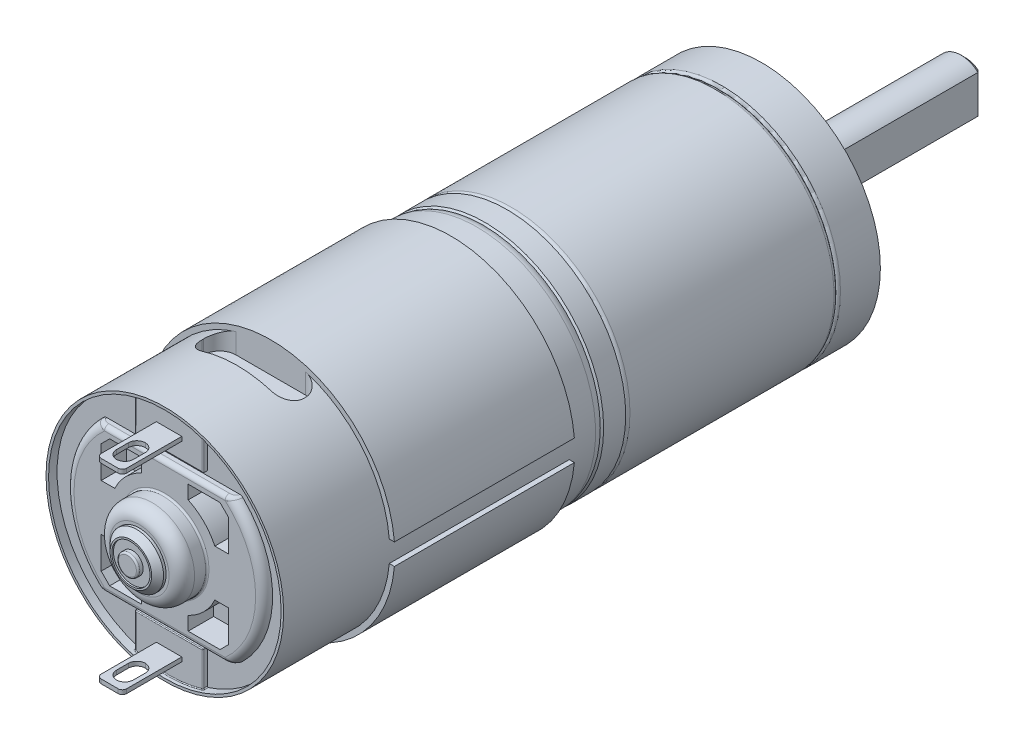
SolidWorks part; units mm, degrees
ref_plane "Front Plane" through (0, 0, 0) normal (0, 0, 1) x (1, 0, 0)
ref_plane "Top Plane" through (0, 0, 0) normal (0, 1, 0) x (1, 0, 0)
ref_plane "Right Plane" through (0, 0, 0) normal (1, 0, 0) x (0, 0, -1)
sketch "Sketch1" plane through (0, 0, 0) normal (0, 0, 1) x (1, 0, 0)
  circle A0 centre (0, 0) radius 14
  dimension "D1" = 28
extrude "Boss-Extrude1" add sketch "Sketch1" along normal blind 5
fillet "Fillet1" radius 0.3 1 edges at (14, 0, 5)
sketch "Sketch2" plane through (0, 0, 5) normal (0, 0, 1) x (1, 0, 0)
  circle A0 centre (0, 0) radius 14
  dimension "D1" = 28
extrude "Boss-Extrude2" add sketch "Sketch2" along normal blind 25
fillet "Fillet2" radius 0.5 2 edges at (14, 0, 30) (14, 0, 5)
sketch "Sketch3" plane through (0, 0, 30) normal (0, 0, 1) x (1, 0, 0)
  circle A0 centre (0, 0) radius 14
extrude "Boss-Extrude3" add sketch "Sketch3" along normal blind 2.8
chamfer "Chamfer1" distance 0.2 angle 45 1 edges at (14, 0, 32.8)
sketch "Sketch4" plane through (0, 0, 32.8) normal (0, 0, 1) x (1, 0, 0)
  circle A0 centre (0, 0) radius 14
extrude "Boss-Extrude4" add sketch "Sketch4" along normal blind 37.5
fillet "Fillet3" radius 1.5 1 edges at (14, 0, 32.8)
sketch "Sketch5" plane through (0, 0, 70.3) normal (0, 0, 1) x (1, 0, 0)
  circle A0 centre (0, 0) radius 13.7
  circle A1 centre (0, 0) radius 14 construction
  dimension "D1" = 0.3
extrude "Cut-Extrude1" cut sketch "Sketch5" against normal blind 1
sketch "Sketch6" plane through (0, 0, 69.3) normal (0, 0, 1) x (1, 0, 0)
  line L0 (0, 8.5) -> (0, -8.5) construction
  line L1 (8.0399, -8.5) -> (-8.0399, -8.5)
  line L2 (8.0399, 8.5) -> (-8.0399, 8.5)
  circle A0 centre (0, 0) radius 11.7
  circle A1 centre (0, 0) radius 13.7 construction
  point P8 (0, 0)
  point P11 (0, -8.5)
  point P14 (0, 8.5)
  dimension "D1" = 2
  dimension "D2" = 17
extrude "Boss-Extrude5" add sketch "Sketch6" along normal blind 1 contours L2 L0 L1 A0 | L0 L2 A0 L1 region at (5.3371, 0, 69.3) region at (-5.3371, 0, 69.3)
fillet "Fillet4" radius 1 2 edges at (-11.7, 0, 70.3) (11.7, 0, 70.3)
fillet "Fillet5" radius 0.5 6 edges at (7.6727, 8.5, 69.9605) (-7.8613, 8.5, 69.7787) (7.8613, -8.5, 69.7787) (-7.6727, -8.5, 69.9605) (0, 8.5, 70.3) (0, -8.5, 70.3)
sketch "Sketch7" plane through (0, 0, 70.3) normal (0, 0, 1) x (1, 0, 0)
  circle A0 centre (0, 0) radius 5
  dimension "D1" = 10
extrude "Boss-Extrude6" add sketch "Sketch7" along normal blind 3
fillet "Fillet6" radius 1.5 1 edges at (5, 0, 73.3)
fillet "Fillet7" radius 0.2 1 edges at (5, 0, 70.3)
sketch "Sketch8" plane through (0, 0, 73.3) normal (0, 0, 1) x (1, 0, 0)
  circle A0 centre (0, 0) radius 2.25
  circle A1 centre (0, 0) radius 3.15
  dimension "D1" = 6.3
  dimension "D2" = 4.5
extrude "Boss-Extrude7" add sketch "Sketch8" along normal blind 1
chamfer "Chamfer2" distance 0.7 angle 45 1 edges at (3.15, 0, 74.3)
sketch "Sketch9" plane through (0, 0, 73.3) normal (0, 0, 1) x (1, 0, 0)
  circle A0 centre (0, 0) radius 2.25
  circle A1 centre (0, 0) radius 1.25
  dimension "D1" = 2.5
extrude "Boss-Extrude8" add sketch "Sketch9" along normal blind 0.8
sketch "Sketch10" plane through (0, 0, 73.3) normal (0, 0, 1) x (1, 0, 0)
  circle A0 centre (0, 0) radius 1.25
extrude "Boss-Extrude10" add sketch "Sketch10" along normal blind 1.4
fillet "Fillet8" radius 0.2 1 edges at (1.25, 0, 74.7)
sketch "Sketch11" plane through (0, 0, 69.3) normal (0, 0, 1) x (1, 0, 0)
  line L0 (0, 9) -> (0, -9)
  line L1 (4, 9) -> (-4, 9)
  line L2 (-4, 9) -> (-4, 13.1031)
  line L3 (4, 9) -> (4, 13.1031)
  line L4 (0, 0) -> (8.5763, 0) construction
  line L5 (4, -9) -> (4, -13.1031)
  line L6 (-4, -9) -> (-4, -13.1031)
  line L7 (4, -9) -> (-4, -9)
  circle A0 centre (0, 0) radius 13.7
  point P7 (0, 0)
  point P14 (0, 9)
  circle M12 centre (0, 0) radius 13.7
  dimension "D3" = 27.4
  dimension "D1" = 18
  dimension "D2" = 8
extrude "Boss-Extrude12" add sketch "Sketch11" along normal blind 0.5 contours L5 L7 L6 M12 | L1 L3 L2 M12 region at (0, 11.2549, 69.3) region at (0, -11.2549, 69.3)
fillet "Fillet9" radius 0.1 12 edges at (-4, 13.1031, 69.55) (4, 13.1031, 69.55) (-4, -13.1031, 69.55) (4, -13.1031, 69.55) (-4, 11.0515, 69.8) (0, 13.7, 69.8) (4, 11.0515, 69.8) (0, 9, 69.8) (0, -13.7, 69.8) (-4, -11.0515, 69.8) (0, -9, 69.8) (4, -11.0515, 69.8)
sketch "Sketch12" plane through (0, 0, 69.8) normal (0, 0, 1) x (1, 0, 0)
  line L0 (0, 0) -> (0, -11.5) construction
  line L1 (-1.5, -11.5) -> (1.5, -11.5)
  line L2 (1.5, -11.5) -> (1.5, -11)
  line L3 (1.5, -11) -> (-1.5, -11)
  line L4 (-1.5, -11) -> (-1.5, -11.5)
  line L5 (0, 0) -> (-7.3114, 0) construction
  line L6 (-1.5, 11) -> (-1.5, 11.5)
  line L7 (1.5, 11) -> (-1.5, 11)
  line L8 (1.5, 11.5) -> (1.5, 11)
  line L9 (-1.5, 11.5) -> (1.5, 11.5)
  point P6 (0, -11.5)
  point P13 (0, 11.5)
  dimension "D1" = 11.5
  dimension "D2" = 3
  dimension "D3" = 0.5
extrude "Boss-Extrude13" add sketch "Sketch12" along normal blind 7
sketch "Sketch13" plane through (0, -11.5, 0) normal (0, -1, 0) x (1, 0, 0)
  line L0 (0, 76.8) -> (0, 70.3) construction
  line L1 (-1.5, 76.8) -> (1.5, 76.8) construction
  line L2 (14, 70.3) -> (-14, 70.3) construction
  line L3 (-1.5, 76.8) -> (-1.5, 69.8) construction
  line L4 (1, 72.6) -> (-1, 72.6)
  line L5 (1, 72.6) -> (1, 76)
  line L6 (1, 76) -> (-1, 76)
  line L7 (-1, 72.6) -> (-1, 76)
  line L8 (1, 72.6) -> (-1, 76) construction
  line L9 (1, 76) -> (-1, 72.6) construction
  point P6 (0, 74.3)
  dimension "D1" = 2.5
  dimension "D2" = 0.8
  dimension "D3" = 0.5
extrude "Cut-Extrude2" cut sketch "Sketch13" against normal blind 1
fillet "Fillet10" radius 0.5 2 edges at (1.5, -11.25, 76.8) (-1.5, -11.25, 76.8)
ref_plane "Plane1" through (0, 0, 0) normal (0, 1, 0) x (1, 0, 0)
mirror "Mirror6" about plane through (0, 0, 0) normal (0, 1, 0) of "Cut-Extrude2"
fillet "Fillet11" radius 0.5 2 edges at (-1.5, 11.25, 76.8) (1.5, 11.25, 76.8)
sketch "Sketch14" plane through (0, 0, 70.3) normal (0, 0, 1) x (1, 0, 0)
  line L1 (7.5, -7.5) -> (-7.5, -7.5)
  line L2 (7.5, -7.5) -> (7.5, 7.5)
  line L3 (7.5, 7.5) -> (-7.5, 7.5)
  line L4 (-7.5, -7.5) -> (-7.5, 7.5)
  line L5 (7.5, -7.5) -> (-7.5, 7.5) construction
  line L6 (7.5, 7.5) -> (-7.5, -7.5) construction
  line L7 (2.75, -19.1882) -> (-2.75, -19.1882)
  line L8 (2.75, -19.1882) -> (2.75, 19.1882)
  line L9 (2.75, 19.1882) -> (-2.75, 19.1882)
  line L10 (-2.75, -19.1882) -> (-2.75, 19.1882)
  line L11 (2.75, -19.1882) -> (-2.75, 19.1882) construction
  line L12 (2.75, 19.1882) -> (-2.75, -19.1882) construction
  line L13 (-15.3123, -2.75) -> (15.3123, -2.75)
  line L14 (-15.3123, -2.75) -> (-15.3123, 2.75)
  line L15 (-15.3123, 2.75) -> (15.3123, 2.75)
  line L16 (15.3123, -2.75) -> (15.3123, 2.75)
  line L17 (-15.3123, -2.75) -> (15.3123, 2.75) construction
  line L18 (-15.3123, 2.75) -> (15.3123, -2.75) construction
  circle A0 centre (0, 0) radius 6.5
  dimension "D1" = 13
  dimension "D2" = 15
  dimension "D3" = 15
  dimension "D4" = 5.5
  dimension "D5" = 5.5
extrude "Cut-Extrude3" cut sketch "Sketch14" against normal blind 3 contours A0 L13 L4 L1 L10 | A0 L10 L3 L4 L15 | A0 L15 L2 L3 L8 | A0 L8 L1 L2 L13 region at (5.5716, -5.5716, 70.3) region at (-5.5716, -5.5716, 70.3) region at (5.5716, 5.5716, 70.3) region at (-5.5716, 5.5716, 70.3)
chamfer "Chamfer3" distance 1 angle 45 4 edges at (-7.5, 7.5, 68.8) (7.5, 7.5, 68.8) (7.5, -7.5, 68.8) (-7.5, -7.5, 68.8)
sketch "Sketch15" plane through (0, 0, 0) normal (0, 0, -1) x (-1, 0, 0)
  circle A0 centre (0, 0) radius 8.5
  circle A1 centre (0, 0) radius 6.5
  dimension "D1" = 17
  dimension "D2" = 13
extrude "Boss-Extrude14" add sketch "Sketch15" along normal blind 1
fillet "Fillet12" radius 0.1 2 edges at (-8.5, 0, -1) (-6.5, 0, -1)
sketch "Sketch16" plane through (0, 0, 0) normal (0, 0, -1) x (-1, 0, 0)
  circle A0 centre (0, 0) radius 6.5
extrude "Boss-Extrude15" add sketch "Sketch16" along normal blind 1
sketch "Sketch17" plane through (0, 0, -1) normal (0, 0, -1) x (-1, 0, 0)
  line L0 (3, 0) -> (-2, 0) construction
  line L1 (15.4, 0) -> (-15.4, 0) construction
  line L2 (-2, 2.2361) -> (-2, -2.2361)
  circle A0 centre (0, 0) radius 3
  point P10 (-2, 0)
  dimension "D1" = 6
  dimension "D2" = 5
extrude "Boss-Extrude16" add sketch "Sketch17" along normal blind 23 contours L0 A0 L2 | A0 L0 L2 region at (-0.296, -1.324, -1) region at (-0.296, 1.324, -1)
sketch "Sketch18" plane through (0, 0, -1) normal (0, 0, -1) x (-1, 0, 0)
  circle A0 centre (0, 0) radius 3
extrude "Boss-Extrude17" add sketch "Sketch18" along normal blind 2
chamfer "Chamfer5" distance 0.5 angle 45 2 edges at (-3, 0, -24) (2, 0, -24)
ref_plane "Plane2" through (0, 0, 57.8) normal (0, 0, 1) x (1, 0, 0)
sketch "Sketch19" plane through (0, 0, 57.8) normal (0, 0, 1) x (1, 0, 0)
  line L0 (14, 0) -> (14.6, 0) construction
  line L1 (14.3, 1.25) -> (14.3, -1.25)
  line L2 (13.9441, 1.25) -> (14.5464, 1.25)
  line L3 (13.9441, -1.25) -> (14.5464, -1.25)
  circle A0 centre (0, 0) radius 14
  circle A1 centre (0, 0) radius 14.6
  point P9 (14.3, 0)
  dimension "D1" = 0.6
  dimension "D3" = 28
  dimension "D2" = 2.5
extrude "Boss-Extrude18" add sketch "Sketch19" against normal blind 21.2 contours L2 A1 L3 A0 region at (14.122, 1.6626, 57.8)
fillet "Fillet13" radius 1 8 edges at (-1, -11.25, 76) (-1, -11.25, 72.6) (1, -11.25, 72.6) (1, -11.25, 76) (1, 11.25, 76) (1, 11.25, 72.6) (-1, 11.25, 72.6) (-1, 11.25, 76)
sketch "Sketch20" plane through (0, 0, 0) normal (0, 1, 0) x (1, 0, 0)
  line L0 (-0.0268, -57.8) -> (-0.0268, -61.8) construction
  line L1 (-14.6, -57.8) -> (14.5464, -57.8) construction
  line L3 (4.0732, -57.8) -> (-4.1268, -57.8)
  line L4 (5.9732, -59.7) -> (5.9732, -59.9)
  line L5 (4.0732, -61.8) -> (-4.1268, -61.8)
  line L6 (-6.0268, -59.7) -> (-6.0268, -59.9)
  line L7 (5.9732, -57.8) -> (-6.0268, -61.8) construction
  line L8 (5.9732, -61.8) -> (-6.0268, -57.8) construction
  arc A0 (-4.1268, -57.8) -> (-6.0268, -59.7) centre (-4.1268, -59.7) ccw
  arc A1 (-4.1268, -61.8) -> (-6.0268, -59.9) centre (-4.1268, -59.9) cw
  arc A2 (5.9732, -59.9) -> (4.0732, -61.8) centre (4.0732, -59.9) cw
  arc A3 (4.0732, -57.8) -> (5.9732, -59.7) centre (4.0732, -59.7) cw
  point P4 (-0.0268, -59.8)
  dimension "D3" = 1.9
  dimension "D1" = 4
  dimension "D2" = 12
extrude "Cut-Extrude4" cut sketch "Sketch20" along normal blind 40.2 and the other way blind 31
sketch "Sketch21" plane through (0, 0, 0) normal (0, 1, 0) x (1, 0, 0)
  line L1 (8.1385, -56.1871) -> (-8.1921, -56.1871)
  line L2 (8.1385, -56.1871) -> (8.1385, -63.3042)
  line L3 (8.1385, -63.3042) -> (-8.1921, -63.3042)
  line L4 (-8.1921, -56.1871) -> (-8.1921, -63.3042)
  line L5 (8.1385, -56.1871) -> (-8.1921, -63.3042) construction
  line L6 (8.1385, -63.3042) -> (-8.1921, -56.1871) construction
  point P0 (-0.0268, -59.7457)
extrude "Boss-Extrude19" add sketch "Sketch21" against normal blind 11.2 and the other way blind 11
sketch "Sketch22" plane through (0, 0, 0) normal (0, 0, -1) x (-1, 0, 0)
  line L0 (0, 11) -> (0, -11)
  circle A0 centre (0, -11) radius 1.5
  circle A1 centre (-11, 0) radius 1.5
  circle A2 centre (0, 11) radius 1.5
  circle A3 centre (11, 0) radius 1.5
  point P4 (0, 0)
  point P15 (0, 0)
  dimension "D2" = 3
  dimension "D1" = 22
  dimension "D3" = 4
extrude "Cut-Extrude5" cut sketch "Sketch22" against normal blind 5 contours A2 | A1 | A3 | A0 region at (-1.0307, -9.9693, 0) region at (1.0307, 12.0307, 0) region at (11, 0, 0) region at (-11, 0, 0)
